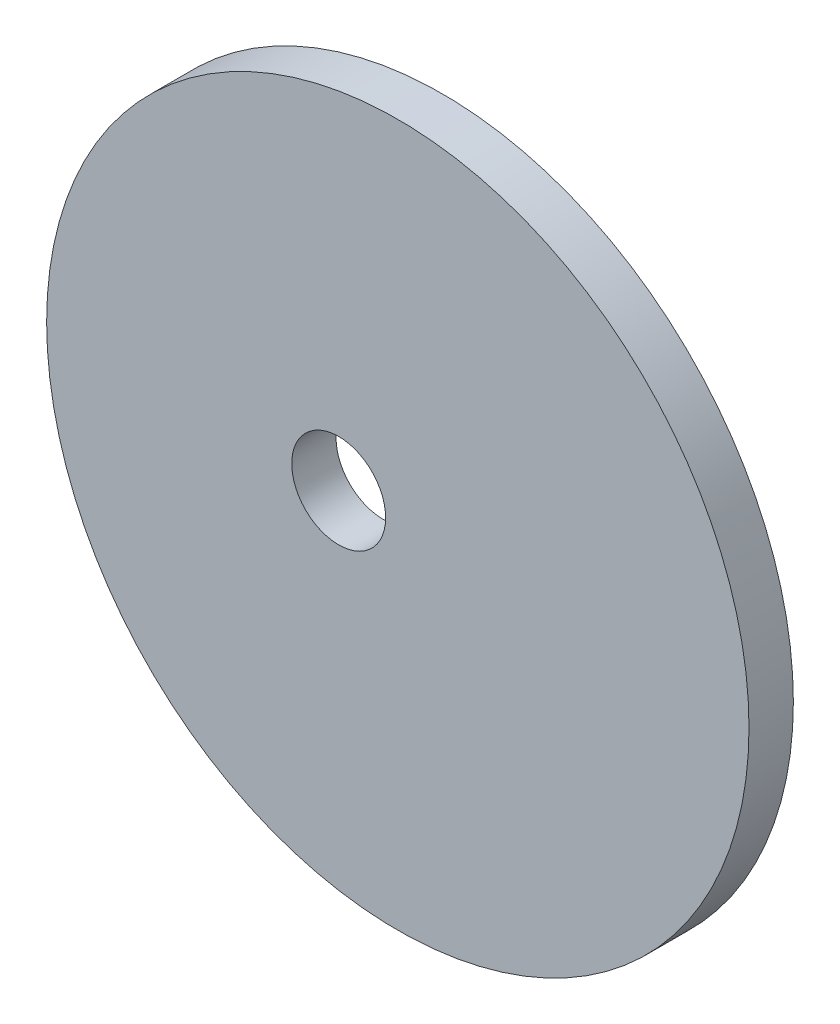
SolidWorks part; units mm, degrees
ref_plane "Front Plane" through (0, 0, 0) normal (0, 0, 1) x (1, 0, 0)
ref_plane "Top Plane" through (0, 0, 0) normal (0, 1, 0) x (1, 0, 0)
ref_plane "Right Plane" through (0, 0, 0) normal (1, 0, 0) x (0, 0, -1)
sketch "Sketch1" plane through (0, 0, 0) normal (0, 0, 1) x (1, 0, 0)
  circle A0 centre (0, 0) radius 23.75
  circle A2 centre (-4, 0) radius 3.175
extrude "Boss-Extrude5" add sketch "Sketch1" along normal blind 3 contours A2 | A0 region at (-4, 0, 0)
sketch "Sketch2" plane through (0, 0, 0) normal (0, 0, 1) x (1, 0, 0)
  circle A0 centre (0, 0) radius 23.75
sketch "Sketch3" plane through (0, 0, 0) normal (0, 0, 1) x (1, 0, 0)
  circle A0 centre (-4, 0) radius 3.175
